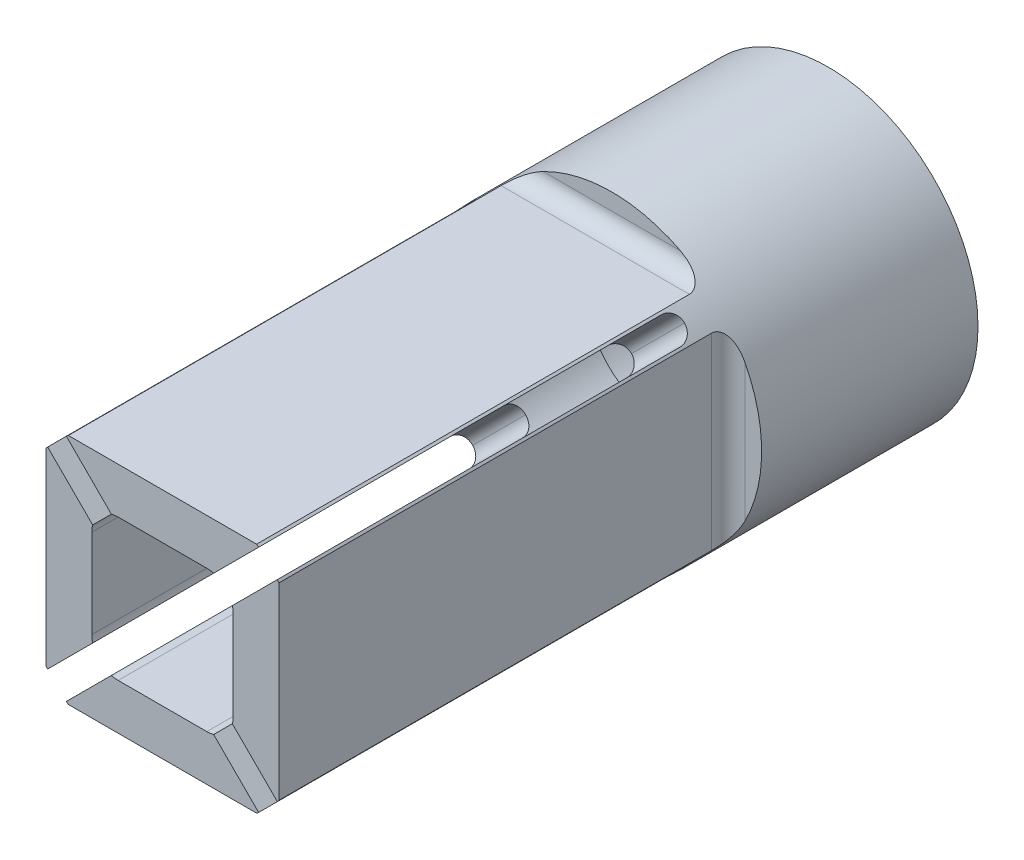
SolidWorks part; units mm, degrees
ref_plane "Front Plane" through (0, 0, 0) normal (0, 0, 1) x (1, 0, 0)
ref_plane "Top Plane" through (0, 0, 0) normal (0, 1, 0) x (1, 0, 0)
ref_plane "Right Plane" through (0, 0, 0) normal (1, 0, 0) x (0, 0, -1)
sketch "Sketch1" plane through (0, 0, 0) normal (0, 0, 1) x (1, 0, 0)
  circle A0 centre (0, 0) radius 9
  circle A1 centre (0, 0) radius 4.25
  dimension "D1" = 18
  dimension "D2" = 8.5
extrude "Boss-Extrude1" add sketch "Sketch1" along normal blind 40
sketch "Sketch2" plane through (0, 0, 0) normal (0, 0, -1) x (-1, 0, 0)
  circle A0 centre (0, 0) radius 4.9022
  dimension "D1" = 9.8044
extrude "Cut-Extrude1" cut sketch "Sketch2" against normal blind 10
ref_plane "Plane1" through (0, 0, 13) normal (0, 0, -1) x (-1, 0, 0)
sketch "Sketch3" plane through (0, 0, 13) normal (0, 0, -1) x (-1, 0, 0)
  line L1 (-7, 7) -> (7, 7)
  line L2 (-7, 7) -> (-7, -7)
  line L3 (-7, -7) -> (7, -7)
  line L4 (7, 7) -> (7, -7)
  line L5 (-7, 7) -> (7, -7) construction
  line L6 (-7, -7) -> (7, 7) construction
  circle A0 centre (0, 0) radius 14.6939
  point P0 (0, 0)
  dimension "D1" = 14
extrude "Cut-Extrude2" cut sketch "Sketch3" against normal blind 40
ref_axis "Axis1" through (0, 0, 40) along (0, 0, -1)
ref_plane "Plane2" through (0, 0, 0) normal (0.7071, 0.7071, 0) x (0, 0, -1)
sketch "Sketch5" plane through (0, 0, 0) normal (0, 0, -1) x (-1, 0, 0)
  circle A0 centre (0, 0) radius 4.5
  dimension "D1" = 9
extrude "Cut-Extrude4" cut sketch "Sketch5" against normal blind 30
fillet "Fillet2" [suppressed] radius 1
sketch "Sketch6" plane through (0, -7, 0) normal (0, -1, 0) x (1, 0, 0)
  line L0 (0, 19) -> (0, 21) construction
  line L1 (-4, 19) -> (-4, 21)
  line L2 (4, 19) -> (4, 21)
  line L3 (-9, 0) -> (9, 0) construction
  arc A0 (-4, 19) -> (4, 19) centre (0, 19) ccw
  arc A1 (4, 21) -> (-4, 21) centre (0, 21) ccw
  point P3 (0, 20)
  dimension "D1" = 8
  dimension "D2" = 2
  dimension "D3" = 20
extrude "Cut-Extrude5" [suppressed] cut sketch "Sketch6" against normal up to surface (10.5 mm away)
sketch "Sketch7" plane through (-7, 0, 0) normal (-1, 0, 0) x (0, 0, 1)
  line L0 (30, -3) -> (30, 3) construction
  line L1 (28, -3) -> (28, 3)
  line L2 (32, -3) -> (32, 3)
  line L4 (0, 9) -> (0, -9) construction
  line L5 (0, 9) -> (0, -9)
  arc A0 (28, -3) -> (32, -3) centre (30, -3) ccw
  arc A1 (32, 3) -> (28, 3) centre (30, 3) ccw
  point P3 (30, 0)
  point P11 (0, 0)
  dimension "D3" = 30
  dimension "D1" = 4
  dimension "D2" = 6
extrude "Cut-Extrude6" [suppressed] cut sketch "Sketch7" against normal through all
sketch "Sketch14" plane through (0, 0, 40) normal (0, 0, 1) x (1, 0, 0)
  line L1 (4.25, -4.25) -> (-4.25, -4.25)
  line L2 (4.25, -4.25) -> (4.25, 4.25)
  line L3 (4.25, 4.25) -> (-4.25, 4.25)
  line L4 (-4.25, -4.25) -> (-4.25, 4.25)
  line L5 (4.25, -4.25) -> (-4.25, 4.25) construction
  line L6 (4.25, 4.25) -> (-4.25, -4.25) construction
  point P0 (0, 0)
  dimension "D1" = 8.5
extrude "Cut-Extrude10" cut sketch "Sketch14" against normal blind 15
fillet "Fillet5" radius 1.5875 4 edges at (-4.25, 4.25, 32.5) (4.25, 4.25, 32.5) (4.25, -4.25, 32.5) (-4.25, -4.25, 32.5)
sketch "Sketch11" plane through (0, 0, 40) normal (0, 0, 1) x (1, 0, 0)
  line L0 (0, 0) -> (-6.8501, 6.8501) construction
  line L1 (-0.5613, -0.5613) -> (-7.4113, 6.2888)
  line L2 (0.5613, 0.5613) -> (-6.2888, 7.4113)
  arc A0 (-0.5613, -0.5613) -> (0.5613, 0.5613) centre (0, 0) ccw
  arc A1 (-6.2888, 7.4113) -> (-7.4113, 6.2888) centre (-6.8501, 6.8501) ccw
  point P3 (-3.425, 3.425)
  dimension "D1" = 1.5875
extrude "Cut-Extrude8" cut sketch "Sketch11" against normal blind 25
fillet "Fillet6" radius 0.7937 2 edges at (-4.1744, 5.2969, 15) (-5.2969, 4.1744, 15)
pattern_circular "CirPattern2" count 4 over 360 about axis through (0, 0, 30) along (0, 0, -1) of "Cut-Extrude8", "Fillet6"
fillet "Fillet4" radius 1 4 edges at (0, -7, 13) (7, 0, 13) (0, 7, 13) (-7, 0, 13)
